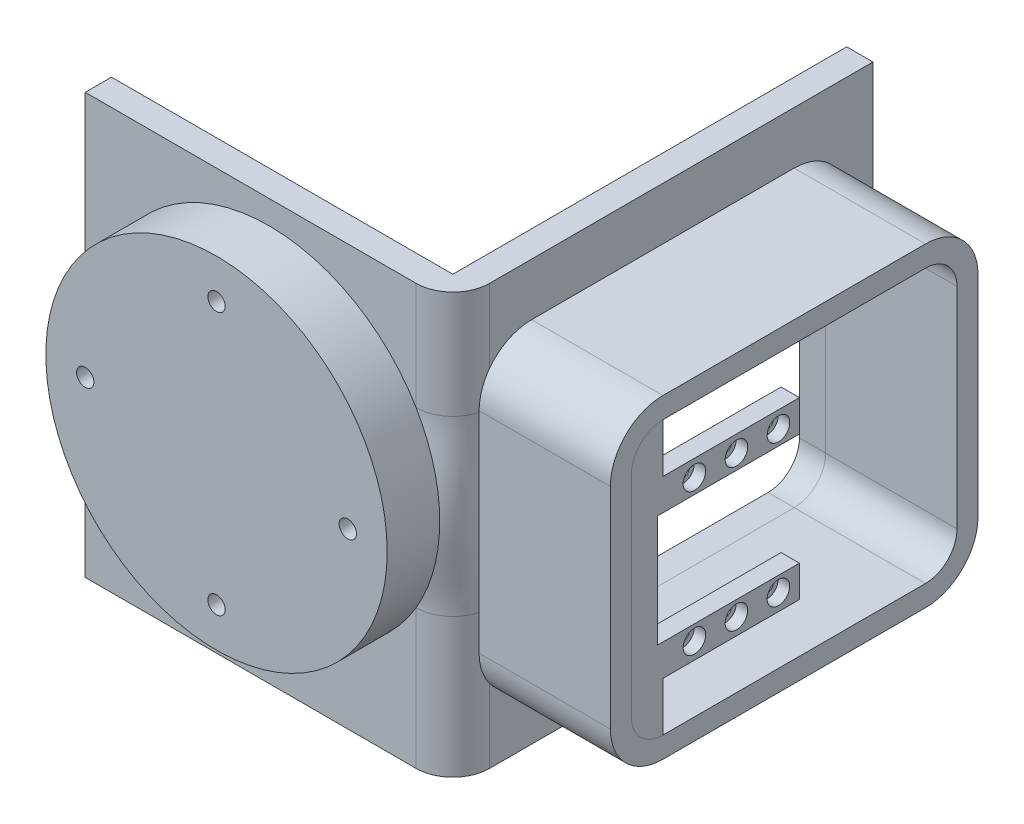
SolidWorks part; units mm, degrees
ref_plane "Front Plane" through (0, 0, 0) normal (0, 0, 1) x (1, 0, 0)
ref_plane "Top Plane" through (0, 0, 0) normal (0, 1, 0) x (1, 0, 0)
ref_plane "Right Plane" through (0, 0, 0) normal (1, 0, 0) x (0, 0, -1)
sketch "Sketch1" plane through (0, 0, 0) normal (0, 0, 1) x (1, 0, 0)
  circle A5 centre (0, 0) radius 32.5
  dimension "D1" = 65
extrude "Boss-Extrude1" add sketch "Sketch1" against normal blind 10
ref_plane "Plane1" through (60, 0, 0) normal (1, 0, 0) x (0, 0, -1)
ref_plane "Plane2" through (60, 0, 0) normal (1, 0, 0) x (0, 0, -1)
sketch "Sketch10" plane through (0, 0, -10) normal (0, 0, -1) x (-1, 0, 0)
  line L0 (0, -3) -> (0, 0) construction
  line L1 (-35, -43) -> (35, -43)
  line L2 (-35, -43) -> (-35, 37)
  line L3 (-35, 37) -> (35, 37)
  line L4 (35, -43) -> (35, 37)
  line L5 (-35, -43) -> (35, 37) construction
  line L6 (-35, 37) -> (35, -43) construction
  point P0 (0, -3)
  dimension "D3" = 3
  dimension "D1" = 80
  dimension "D2" = 70
extrude "Boss-Extrude6" add sketch "Sketch10" along normal blind 80
sketch "Sketch2" plane through (60, 0, 0) normal (1, 0, 0) x (0, 0, -1)
  line L2 (0, -3) -> (146.6861, -3) construction
  line L3 (50, -3) -> (50, 30) construction
  line L5 (10, 37) -> (10, -43) construction
  line L6 (90, 37) -> (90, -43) construction
  line L7 (25, -33) -> (75, -33)
  line L8 (15, -23) -> (15, 17)
  line L9 (25, 27) -> (75, 27)
  line L10 (85, -23) -> (85, 17)
  line L11 (15, -33) -> (85, 27) construction
  line L12 (15, 27) -> (85, -33) construction
  arc A1 (25, -33) -> (15, -23) centre (25, -23) cw
  arc A2 (75, -33) -> (85, -23) centre (75, -23) ccw
  arc A3 (75, 27) -> (85, 17) centre (75, 17) cw
  arc A4 (15, 17) -> (25, 27) centre (25, 17) cw
  point P0 (90, -3)
  dimension "D1" = 70
  dimension "D3" = 10
  dimension "D2" = 60
extrude "Boss-Extrude2" add sketch "Sketch2" against normal up to surface (25 mm away) separate body up to face at (35, -3, -50)
sketch "Sketch11" plane through (0, 37, 0) normal (0, 1, 0) x (1, 0, 0)
  line L1 (-35, 90) -> (30, 90)
  line L2 (-35, 90) -> (-35, 15)
  line L3 (-35, 15) -> (30, 15)
  line L4 (30, 90) -> (30, 15)
  dimension "D1" = 75
  dimension "D2" = 65
extrude "Cut-Extrude5" cut sketch "Sketch11" against normal through all
sketch "Sketch4" plane through (35, 0, 0) normal (-1, 0, 0) x (0, 0, 1)
  line L8 (-75, -29) -> (-25, -29)
  line L9 (-81, 17) -> (-81, -23)
  line L10 (-25, 23) -> (-75, 23)
  line L11 (-19, -23) -> (-19, 17)
  line L12 (-75, -29) -> (-25, -29)
  line L13 (-81, 17) -> (-81, -23)
  line L14 (-25, 23) -> (-75, 23)
  line L15 (-19, -23) -> (-19, 17)
  arc A10 (-81, -23) -> (-75, -29) centre (-75, -23) ccw
  arc A11 (-75, 23) -> (-81, 17) centre (-75, 17) ccw
  arc A12 (-19, 17) -> (-25, 23) centre (-25, 17) ccw
  arc A13 (-25, -29) -> (-19, -23) centre (-25, -23) ccw
  arc A14 (-81, -23) -> (-75, -29) centre (-75, -23) ccw
  arc A15 (-75, 23) -> (-81, 17) centre (-75, 17) ccw
  arc A16 (-19, 17) -> (-25, 23) centre (-25, 17) ccw
  arc A17 (-25, -29) -> (-19, -23) centre (-25, -23) ccw
  dimension "D1" = 4
extrude "Cut-Extrude2" cut sketch "Sketch4" against normal through all contours L12 A17 L15 A16 L14 A15 L13 A14 region at (35, -3, -50)
sketch "Sketch5" plane through (60, 0, 0) normal (1, 0, 0) x (0, 0, -1)
  line L0 (54, -3) -> (19, -3) construction
  line L1 (51, 13.65) -> (51, 7.65)
  line L2 (51, 7.65) -> (24, 7.65)
  line L3 (24, 7.65) -> (24, -13.65)
  line L4 (24, -13.65) -> (51, -13.65)
  line L5 (51, -13.65) -> (51, -19.65)
  line L6 (51, -19.65) -> (25, -19.65)
  line L8 (51, 13.65) -> (25, 13.65)
  line L10 (54, -3) -> (54, -16.5) construction
  line L11 (54, -16.5) -> (47, -16.5) construction
  line L12 (47, -16.5) -> (39, -16.5) construction
  line L13 (39, -16.5) -> (31, -16.5) construction
  line L15 (19, 17) -> (19, -23)
  line L16 (25, 13.65) -> (25, 23)
  line L17 (25, -19.65) -> (25, -29)
  line L18 (19, -23) -> (19, 17) construction
  circle A0 centre (54, -3) radius 11 construction
  arc A1 (25, 23) -> (19, 17) centre (25, 17) ccw construction
  circle A2 centre (47, -16.5) radius 1.25
  arc A3 (25, 23) -> (19, 17) centre (25, 17) ccw
  circle A5 centre (39, -16.5) radius 1.25
  circle A6 centre (31, -16.5) radius 1.25
  circle A7 centre (47, 10.5) radius 1.25
  circle A8 centre (39, 10.5) radius 1.25
  circle A9 centre (31, 10.5) radius 1.25
  arc A10 (19, -23) -> (25, -29) centre (25, -23) ccw
  point P8 (24, -3)
  point P17 (0, 0)
  point P19 (0, 0)
  point P31 (50, 31)
  point P36 (44, 25)
  point P44 (44, -20.7232)
  point P45 (44, -25)
  point P46 (50.2808, 16.65)
  point P47 (0, 0)
  point P48 (44, 0)
  point P49 (50.2808, 17.5458)
  point P50 (0, 0)
  point P51 (50, -31)
  point P53 (67.5313, 13.5)
  dimension "D1" = 22
  dimension "D6" = 2.5
  dimension "D3" = 21.3
  dimension "D4" = 13.5
  dimension "D5" = 7
  dimension "D7" = 8
  dimension "D8" = 8
  dimension "D9" = 6
  dimension "D10" = 5
  dimension "D12" = 3
  dimension "D2" = 30
extrude "Boss-Extrude3" add sketch "Sketch5" against normal blind 3.5
sketch "Sketch13" plane through (35, 0, 0) normal (1, 0, 0) x (0, 0, -1)
  line L4 (19, 17) -> (19, -23)
  line L5 (25, -29) -> (75, -29)
  line L6 (81, -23) -> (81, 17)
  line L7 (75, 23) -> (25, 23)
  line L8 (19, 17) -> (19, -23)
  line L9 (25, -29) -> (75, -29)
  line L10 (81, -23) -> (81, 17)
  line L11 (75, 23) -> (25, 23)
  arc A6 (25, 23) -> (19, 17) centre (25, 17) ccw
  arc A7 (19, -23) -> (25, -29) centre (25, -23) ccw
  arc A8 (75, -29) -> (81, -23) centre (75, -23) ccw
  arc A9 (81, 17) -> (75, 23) centre (75, 17) ccw
  arc A10 (25, 23) -> (19, 17) centre (25, 17) ccw
  arc A11 (19, -23) -> (25, -29) centre (25, -23) ccw
  arc A12 (75, -29) -> (81, -23) centre (75, -23) ccw
  arc A13 (81, 17) -> (75, 23) centre (75, 17) ccw
  dimension "D1" = 0
extrude "Cut-Extrude6" cut sketch "Sketch13" against normal up to surface (5 mm away) up to face at (30, -3, -52.5)
sketch "Sketch14" plane through (0, 0, 0) normal (0, 0, 1) x (1, 0, 0)
  circle A2 centre (0, 0) radius 28.5
  circle A3 centre (0, 0) radius 28.5
  dimension "D1" = 4
sketch "Sketch16" plane through (60, 0, 0) normal (1, 0, 0) x (0, 0, -1)
  circle A0 centre (47, -16.5) radius 2.15
  circle A1 centre (39, -16.5) radius 2.15
  circle A2 centre (31, -16.5) radius 2.15
  circle A3 centre (31, 10.5) radius 2.15
  circle A4 centre (39, 10.5) radius 2.15
  circle A5 centre (47, 10.5) radius 2.15
  dimension "D1" = 4.3
extrude "Cut-Extrude8" cut sketch "Sketch16" against normal blind 2.2
fillet "Fillet1" radius 7 1 edges at (35, -3, -10)
fillet "Fillet2" [suppressed] radius 10
sketch "Sketch17" plane through (0, 0, -15) normal (0, 0, -1) x (-1, 0, 0)
  line L0 (-25, 0) -> (0, 0) construction
  line L1 (0, 25) -> (0, 0) construction
  line L2 (25, 0) -> (0, 0) construction
  line L3 (0, -25) -> (0, 0) construction
  circle A0 centre (-25, 0) radius 1.65
  circle A1 centre (0, 25) radius 1.65
  circle A2 centre (25, 0) radius 1.65
  circle A3 centre (0, -25) radius 1.65
  point P10 (0, 0)
  point P17 (0, 0)
  dimension "D4" = 3.3
  dimension "D3" = 25
  dimension "D1" = 4
  dimension "D2" = 4
extrude "Cut-Extrude9" cut sketch "Sketch17" against normal through all
